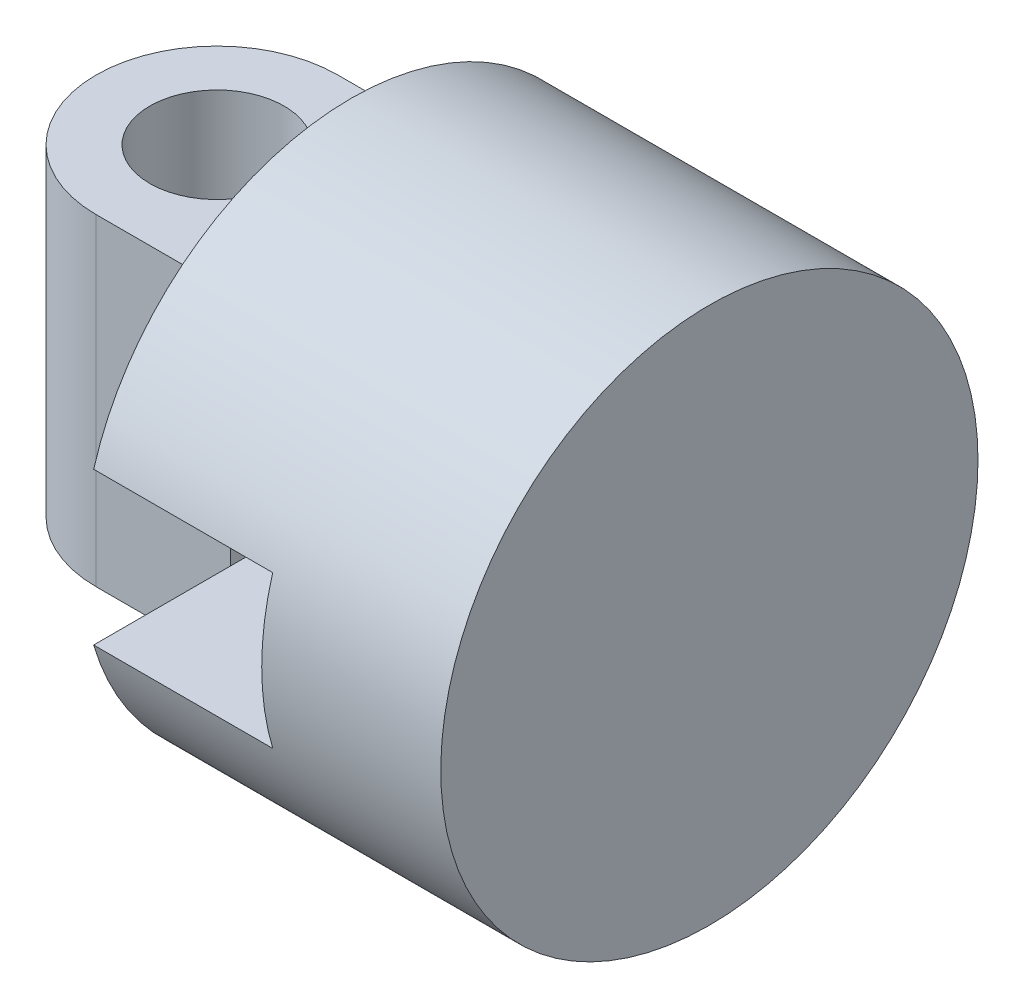
SolidWorks part; units mm, degrees
ref_plane "Спереди" through (0, 0, 0) normal (0, 0, 1) x (1, 0, 0)
ref_plane "Сверху" through (0, 0, 0) normal (0, 1, 0) x (1, 0, 0)
ref_plane "Справа" through (0, 0, 0) normal (1, 0, 0) x (0, 0, -1)
sketch "Эскиз1" plane through (0, 0, 0) normal (1, 0, 0) x (0, 0, -1)
  circle A0 centre (0, 0) radius 30
  dimension "D1" = 60
extrude "Бобышка-Вытянуть1" add sketch "Эскиз1" along normal blind 40
sketch "Эскиз2" plane through (0, 0, 0) normal (0, 1, 0) x (1, 0, 0)
  line L0 (-15, 13.5) -> (0, 13.5)
  line L1 (0, 30) -> (0, -30) construction
  line L2 (0, 13.5) -> (0, -13.5)
  line L3 (0, -13.5) -> (-15, -13.5)
  circle A0 centre (-15, 0) radius 13.5
  circle A1 centre (-15, 0) radius 7.5
  dimension "D3" = 15
  dimension "D1" = 15
  dimension "D2" = 27
extrude "Бобышка-Вытянуть2" add sketch "Эскиз2" along normal blind 18 and the other way blind 18 contours A0 L3 L2 L0 | A0 A1 region at (-7.5, 0, -13.1911) region at (-5.7241, 0, -9.2759)
sketch "Эскиз3" plane through (0, 0, 0) normal (0, 0, 1) x (1, 0, 0)
  line L0 (0, 30) -> (0, -30) construction
  line L1 (20, -8.5) -> (0, -8.5)
  line L2 (20, -8.5) -> (20, 8.5)
  line L3 (20, 8.5) -> (0, 8.5)
  line L4 (0, -8.5) -> (0, 8.5)
  line L5 (20, -8.5) -> (0, 8.5) construction
  line L6 (20, 8.5) -> (0, -8.5) construction
  point P0 (10, 0)
  dimension "D1" = 20
  dimension "D2" = 17
extrude "Вырез-Вытянуть1" cut sketch "Эскиз3" against normal through all and the other way through all
